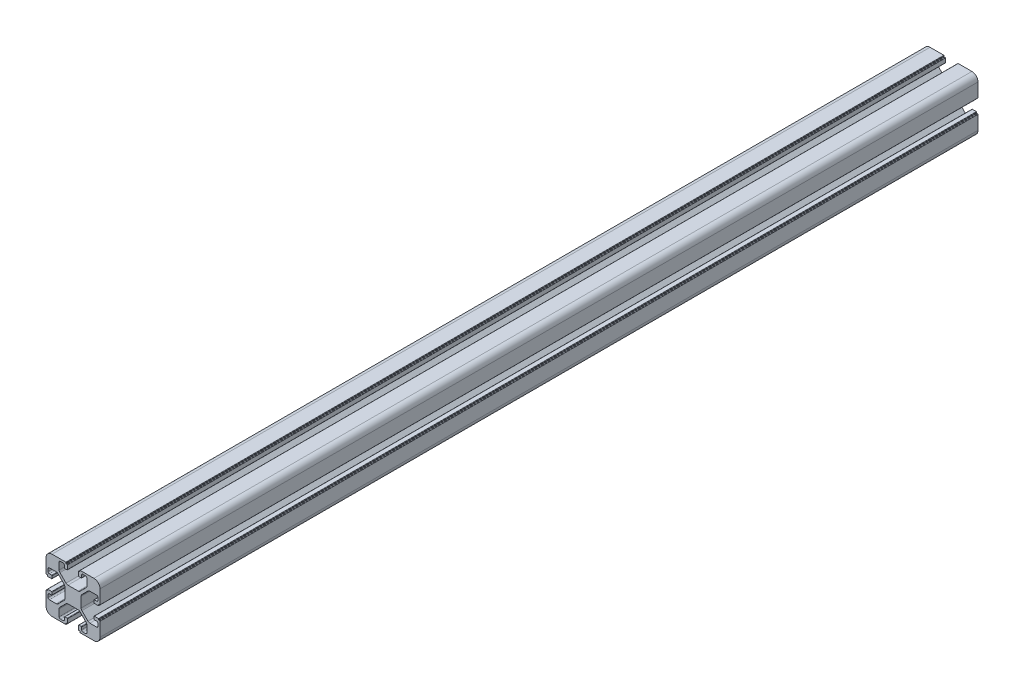
SolidWorks part; units mm, degrees
material "6063-T5"
ref_plane "Front Plane" through (0, 0, 0) normal (0, 0, 1) x (1, 0, 0)
ref_plane "Top Plane" through (0, 0, 0) normal (0, 1, 0) x (1, 0, 0)
ref_plane "Right Plane" through (0, 0, 0) normal (1, 0, 0) x (0, 0, -1)
sketch "Sketch2" plane through (0, 0, 0) normal (0, 0, 1) x (1, 0, 0)
  line L0 (4.5, 0) -> (14.7, 0)
  line L1 (40, 4.5) -> (40, 14.7)
  line L2 (35.5, 40) -> (25.3, 40)
  line L3 (0, 35.5) -> (0, 25.3)
  line L4 (15.9, 1.2) -> (15.9, 4.2)
  line L5 (24.1, 1.2) -> (24.1, 4.2)
  line L6 (38.8, 24.1) -> (35.8, 24.1)
  line L7 (35.5, 24.4) -> (35.5, 26.1)
  line L8 (14, 23.7574) -> (14, 16.2426)
  line L9 (16.2426, 14) -> (23.7574, 14)
  line L10 (26, 16.2426) -> (26, 23.7574)
  line L11 (13.4142, 14.8284) -> (8.9216, 10.3358)
  line L12 (23.7574, 26) -> (16.2426, 26)
  line L13 (4.5, 24.4) -> (4.5, 26.1)
  line L14 (1.2, 24.1) -> (4.2, 24.1)
  line L15 (15.9, 38.8) -> (15.9, 35.8)
  line L16 (14.8284, 26.5858) -> (10.3358, 31.0784)
  line L17 (13.4142, 25.1716) -> (8.9216, 29.6642)
  line L18 (14.8284, 13.4142) -> (10.3358, 8.9216)
  line L19 (25.1716, 13.4142) -> (29.6642, 8.9216)
  line L20 (26.5858, 14.8284) -> (31.0784, 10.3358)
  line L21 (26.5858, 25.1716) -> (31.0784, 29.6642)
  line L22 (25.1716, 26.5858) -> (29.6642, 31.0784)
  line L23 (24.1, 38.8) -> (24.1, 35.8)
  line L24 (14.7, 40) -> (4.5, 40)
  line L25 (25.3, 0) -> (35.5, 0)
  line L26 (38.8, 15.9) -> (35.8, 15.9)
  line L27 (40, 25.3) -> (40, 35.5)
  line L28 (1.2, 15.9) -> (4.2, 15.9)
  line L29 (0, 14.7) -> (0, 4.5)
  line L30 (4.5, 15.6) -> (4.5, 13.9)
  line L31 (35.5, 15.6) -> (35.5, 13.9)
  line L32 (15.6, 35.5) -> (13.9, 35.5)
  line L33 (24.4, 35.5) -> (26.1, 35.5)
  line L34 (15.6, 4.5) -> (13.9, 4.5)
  line L35 (24.4, 4.5) -> (26.1, 4.5)
  line L36 (12.6, 38.5) -> (10.75, 38.5)
  line L37 (1.5, 12.6) -> (1.5, 10.75)
  line L38 (27.4, 1.5) -> (29.25, 1.5)
  line L39 (38.5, 27.4) -> (38.5, 29.25)
  line L40 (38.5, 10.75) -> (38.5, 12.6)
  line L41 (29.25, 38.5) -> (27.4, 38.5)
  line L42 (1.5, 29.25) -> (1.5, 27.4)
  line L43 (10.75, 1.5) -> (12.6, 1.5)
  line L44 (35.8, 26.4) -> (37.5, 26.4)
  line L45 (35.8, 13.6) -> (37.5, 13.6)
  line L46 (4.2, 26.4) -> (2.5, 26.4)
  line L47 (13.6, 35.8) -> (13.6, 37.5)
  line L48 (26.4, 35.8) -> (26.4, 37.5)
  line L49 (4.2, 13.6) -> (2.5, 13.6)
  line L50 (13.6, 4.2) -> (13.6, 2.5)
  line L51 (26.4, 4.2) -> (26.4, 2.5)
  line L52 (9.75, 7.5074) -> (9.75, 2.5)
  line L53 (30.25, 7.5074) -> (30.25, 2.5)
  line L54 (9.75, 37.5) -> (9.75, 32.4926)
  line L55 (30.25, 37.5) -> (30.25, 32.4926)
  line L56 (32.4926, 30.25) -> (37.5, 30.25)
  line L57 (37.5, 9.75) -> (32.4926, 9.75)
  line L58 (2.5, 30.25) -> (7.5074, 30.25)
  line L59 (2.5, 9.75) -> (7.5074, 9.75)
  line L60 (31.55, 37.7) -> (31.55, 32.55)
  line L61 (32.55, 31.55) -> (37.7, 31.55)
  line L62 (1.3, 35.5) -> (1.3, 32.55)
  line L63 (4.5, 38.7) -> (7.45, 38.7)
  line L64 (32.55, 38.7) -> (35.5, 38.7)
  line L65 (38.7, 35.5) -> (38.7, 32.55)
  line L66 (8.45, 37.7) -> (8.45, 32.55)
  line L67 (2.3, 31.55) -> (7.45, 31.55)
  line L68 (1.3, 7.45) -> (1.3, 4.5)
  line L69 (2.3, 8.45) -> (7.45, 8.45)
  line L70 (8.45, 7.45) -> (8.45, 2.3)
  line L71 (4.5, 1.3) -> (7.45, 1.3)
  line L72 (31.55, 7.45) -> (31.55, 2.3)
  line L73 (32.55, 8.45) -> (37.7, 8.45)
  line L74 (38.7, 7.45) -> (38.7, 4.5)
  line L75 (32.55, 1.3) -> (35.5, 1.3)
  line L77 (14.9, 39.8) -> (14.9, 39.2)
  line L78 (15.1, 39) -> (15.7, 39)
  line L79 (25.1, 39.8) -> (25.1, 39.2)
  line L80 (24.9, 39) -> (24.3, 39)
  line L81 (25.1, 0.2) -> (25.1, 0.8)
  line L82 (24.9, 1) -> (24.3, 1)
  line L83 (14.9, 0.2) -> (14.9, 0.8)
  line L84 (15.1, 1) -> (15.7, 1)
  line L85 (0.2, 25.1) -> (0.8, 25.1)
  line L86 (1, 24.9) -> (1, 24.3)
  line L87 (0.2, 14.9) -> (0.8, 14.9)
  line L88 (1, 15.1) -> (1, 15.7)
  line L89 (39.8, 25.1) -> (39.2, 25.1)
  line L90 (39, 24.9) -> (39, 24.3)
  line L91 (39, 15.7) -> (39, 15.1)
  line L92 (39.2, 14.9) -> (39.8, 14.9)
  circle A0 centre (20, 20) radius 3.4
  arc A1 (1.3, 35.5) -> (4.5, 38.7) centre (4.5, 35.5) cw
  arc A2 (1.3, 4.5) -> (4.5, 1.3) centre (4.5, 4.5) ccw
  arc A3 (38.7, 4.5) -> (35.5, 1.3) centre (35.5, 4.5) cw
  arc A4 (35.5, 38.7) -> (38.7, 35.5) centre (35.5, 35.5) cw
  arc A5 (40, 35.5) -> (35.5, 40) centre (35.5, 35.5) ccw
  arc A6 (35.5, 0) -> (40, 4.5) centre (35.5, 4.5) ccw
  arc A7 (4.5, 0) -> (0, 4.5) centre (4.5, 4.5) cw
  arc A8 (4.5, 40) -> (0, 35.5) centre (4.5, 35.5) ccw
  arc A9 (13.4142, 14.8284) -> (14, 16.2426) centre (12, 16.2426) ccw
  arc A10 (7.5074, 9.75) -> (8.9216, 10.3358) centre (7.5074, 11.75) ccw
  arc A11 (9.75, 7.5074) -> (10.3358, 8.9216) centre (11.75, 7.5074) cw
  arc A12 (30.25, 7.5074) -> (29.6642, 8.9216) centre (28.25, 7.5074) ccw
  arc A13 (14.8284, 13.4142) -> (16.2426, 14) centre (16.2426, 12) cw
  arc A14 (25.1716, 13.4142) -> (23.7574, 14) centre (23.7574, 12) ccw
  arc A15 (32.4926, 9.75) -> (31.0784, 10.3358) centre (32.4926, 11.75) cw
  arc A16 (26.5858, 14.8284) -> (26, 16.2426) centre (28, 16.2426) cw
  arc A17 (32.4926, 30.25) -> (31.0784, 29.6642) centre (32.4926, 28.25) ccw
  arc A18 (26.5858, 25.1716) -> (26, 23.7574) centre (28, 23.7574) ccw
  arc A19 (13.4142, 25.1716) -> (14, 23.7574) centre (12, 23.7574) cw
  arc A20 (7.5074, 30.25) -> (8.9216, 29.6642) centre (7.5074, 28.25) cw
  arc A21 (9.75, 32.4926) -> (10.3358, 31.0784) centre (11.75, 32.4926) ccw
  arc A22 (30.25, 32.4926) -> (29.6642, 31.0784) centre (28.25, 32.4926) cw
  arc A23 (25.1716, 26.5858) -> (23.7574, 26) centre (23.7574, 28) cw
  arc A24 (14.8284, 26.5858) -> (16.2426, 26) centre (16.2426, 28) ccw
  arc A25 (37.7, 8.45) -> (38.7, 7.45) centre (37.7, 7.45) cw
  arc A26 (31.55, 2.3) -> (32.55, 1.3) centre (32.55, 2.3) ccw
  arc A27 (31.55, 7.45) -> (32.55, 8.45) centre (32.55, 7.45) cw
  arc A28 (8.45, 2.3) -> (7.45, 1.3) centre (7.45, 2.3) cw
  arc A29 (1.3, 7.45) -> (2.3, 8.45) centre (2.3, 7.45) cw
  arc A30 (7.45, 8.45) -> (8.45, 7.45) centre (7.45, 7.45) cw
  arc A31 (38.7, 32.55) -> (37.7, 31.55) centre (37.7, 32.55) cw
  arc A32 (31.55, 32.55) -> (32.55, 31.55) centre (32.55, 32.55) ccw
  arc A33 (31.55, 37.7) -> (32.55, 38.7) centre (32.55, 37.7) cw
  arc A34 (7.45, 38.7) -> (8.45, 37.7) centre (7.45, 37.7) cw
  arc A35 (8.45, 32.55) -> (7.45, 31.55) centre (7.45, 32.55) cw
  arc A36 (1.3, 32.55) -> (2.3, 31.55) centre (2.3, 32.55) ccw
  arc A37 (30.25, 2.5) -> (29.25, 1.5) centre (29.25, 2.5) cw
  arc A38 (26.4, 2.5) -> (27.4, 1.5) centre (27.4, 2.5) ccw
  arc A39 (13.6, 2.5) -> (12.6, 1.5) centre (12.6, 2.5) cw
  arc A40 (9.75, 2.5) -> (10.75, 1.5) centre (10.75, 2.5) ccw
  arc A41 (26.4, 37.5) -> (27.4, 38.5) centre (27.4, 37.5) cw
  arc A42 (30.25, 37.5) -> (29.25, 38.5) centre (29.25, 37.5) ccw
  arc A43 (37.5, 26.4) -> (38.5, 27.4) centre (37.5, 27.4) ccw
  arc A44 (37.5, 30.25) -> (38.5, 29.25) centre (37.5, 29.25) cw
  arc A45 (37.5, 13.6) -> (38.5, 12.6) centre (37.5, 12.6) cw
  arc A46 (37.5, 9.75) -> (38.5, 10.75) centre (37.5, 10.75) ccw
  arc A47 (2.5, 9.75) -> (1.5, 10.75) centre (2.5, 10.75) cw
  arc A48 (2.5, 13.6) -> (1.5, 12.6) centre (2.5, 12.6) ccw
  arc A49 (2.5, 26.4) -> (1.5, 27.4) centre (2.5, 27.4) cw
  arc A50 (2.5, 30.25) -> (1.5, 29.25) centre (2.5, 29.25) ccw
  arc A51 (9.75, 37.5) -> (10.75, 38.5) centre (10.75, 37.5) cw
  arc A52 (13.6, 37.5) -> (12.6, 38.5) centre (12.6, 37.5) ccw
  arc A53 (26.1, 35.5) -> (26.4, 35.8) centre (26.1, 35.8) ccw
  arc A54 (24.1, 35.8) -> (24.4, 35.5) centre (24.4, 35.8) ccw
  arc A55 (15.9, 35.8) -> (15.6, 35.5) centre (15.6, 35.8) cw
  arc A56 (13.9, 35.5) -> (13.6, 35.8) centre (13.9, 35.8) cw
  arc A57 (13.9, 4.5) -> (13.6, 4.2) centre (13.9, 4.2) ccw
  arc A58 (15.9, 4.2) -> (15.6, 4.5) centre (15.6, 4.2) ccw
  arc A59 (24.1, 4.2) -> (24.4, 4.5) centre (24.4, 4.2) cw
  arc A60 (26.1, 4.5) -> (26.4, 4.2) centre (26.1, 4.2) cw
  arc A61 (35.5, 13.9) -> (35.8, 13.6) centre (35.8, 13.9) ccw
  arc A62 (35.8, 15.9) -> (35.5, 15.6) centre (35.8, 15.6) ccw
  arc A63 (35.8, 24.1) -> (35.5, 24.4) centre (35.8, 24.4) cw
  arc A64 (35.5, 26.1) -> (35.8, 26.4) centre (35.8, 26.1) cw
  arc A65 (4.5, 13.9) -> (4.2, 13.6) centre (4.2, 13.9) cw
  arc A66 (4.2, 15.9) -> (4.5, 15.6) centre (4.2, 15.6) cw
  arc A67 (4.2, 24.1) -> (4.5, 24.4) centre (4.2, 24.4) ccw
  arc A68 (4.5, 26.1) -> (4.2, 26.4) centre (4.2, 26.1) ccw
  arc A69 (25.3, 0) -> (25.1, 0.2) centre (25.3, 0.2) cw
  arc A70 (25.1, 0.8) -> (24.9, 1) centre (24.9, 0.8) ccw
  arc A71 (24.3, 1) -> (24.1, 1.2) centre (24.3, 1.2) cw
  arc A72 (14.7, 0) -> (14.9, 0.2) centre (14.7, 0.2) ccw
  arc A73 (14.9, 0.8) -> (15.1, 1) centre (15.1, 0.8) cw
  arc A74 (15.7, 1) -> (15.9, 1.2) centre (15.7, 1.2) ccw
  arc A75 (39.8, 14.9) -> (40, 14.7) centre (39.8, 14.7) cw
  arc A76 (39, 15.1) -> (39.2, 14.9) centre (39.2, 15.1) ccw
  arc A77 (38.8, 15.9) -> (39, 15.7) centre (38.8, 15.7) cw
  arc A78 (0, 25.3) -> (0.2, 25.1) centre (0.2, 25.3) ccw
  arc A79 (0.8, 25.1) -> (1, 24.9) centre (0.8, 24.9) cw
  arc A80 (1, 24.3) -> (1.2, 24.1) centre (1.2, 24.3) ccw
  arc A81 (0, 14.7) -> (0.2, 14.9) centre (0.2, 14.7) cw
  arc A82 (0.8, 14.9) -> (1, 15.1) centre (0.8, 15.1) ccw
  arc A83 (1, 15.7) -> (1.2, 15.9) centre (1.2, 15.7) cw
  arc A84 (39, 24.3) -> (38.8, 24.1) centre (38.8, 24.3) cw
  arc A85 (39.2, 25.1) -> (39, 24.9) centre (39.2, 24.9) ccw
  arc A86 (40, 25.3) -> (39.8, 25.1) centre (39.8, 25.3) cw
  arc A87 (24.3, 39) -> (24.1, 38.8) centre (24.3, 38.8) ccw
  arc A88 (25.1, 39.2) -> (24.9, 39) centre (24.9, 39.2) cw
  arc A89 (25.3, 40) -> (25.1, 39.8) centre (25.3, 39.8) ccw
  arc A90 (14.9, 39.2) -> (15.1, 39) centre (15.1, 39.2) ccw
  arc A91 (15.7, 39) -> (15.9, 38.8) centre (15.7, 38.8) cw
  arc A92 (14.7, 40) -> (14.9, 39.8) centre (14.7, 39.8) cw
  point P93 (0, 0)
extrude "Boss-Extrude1" add sketch "Sketch2" along normal blind 50
sketch "Sketch3" plane through (0, 0, 50) normal (0, 0, 1) x (1, 0, 0)
  line L76 (25.3, 0) -> (35.5, 0)
  line L77 (40, 4.5) -> (40, 14.7)
  line L78 (39.8, 14.9) -> (39.2, 14.9)
  line L79 (39, 15.1) -> (39, 15.7)
  line L80 (38.8, 15.9) -> (35.8, 15.9)
  line L81 (35.5, 15.6) -> (35.5, 13.9)
  line L82 (35.8, 13.6) -> (37.5, 13.6)
  line L83 (38.5, 12.6) -> (38.5, 10.75)
  line L84 (37.5, 9.75) -> (32.4926, 9.75)
  line L85 (31.0784, 10.3358) -> (26.5858, 14.8284)
  line L86 (26, 16.2426) -> (26, 23.7574)
  line L87 (26.5858, 25.1716) -> (31.0784, 29.6642)
  line L88 (32.4926, 30.25) -> (37.5, 30.25)
  line L89 (38.5, 29.25) -> (38.5, 27.4)
  line L90 (37.5, 26.4) -> (35.8, 26.4)
  line L91 (35.5, 26.1) -> (35.5, 24.4)
  line L92 (35.8, 24.1) -> (38.8, 24.1)
  line L93 (39, 24.3) -> (39, 24.9)
  line L94 (39.2, 25.1) -> (39.8, 25.1)
  line L95 (40, 25.3) -> (40, 35.5)
  line L96 (35.5, 40) -> (25.3, 40)
  line L97 (25.1, 39.8) -> (25.1, 39.2)
  line L98 (24.9, 39) -> (24.3, 39)
  line L99 (24.1, 38.8) -> (24.1, 35.8)
  line L100 (24.4, 35.5) -> (26.1, 35.5)
  line L101 (26.4, 35.8) -> (26.4, 37.5)
  line L102 (27.4, 38.5) -> (29.25, 38.5)
  line L103 (30.25, 37.5) -> (30.25, 32.4926)
  line L104 (29.6642, 31.0784) -> (25.1716, 26.5858)
  line L105 (23.7574, 26) -> (16.2426, 26)
  line L106 (14.8284, 26.5858) -> (10.3358, 31.0784)
  line L107 (9.75, 32.4926) -> (9.75, 37.5)
  line L108 (10.75, 38.5) -> (12.6, 38.5)
  line L109 (13.6, 37.5) -> (13.6, 35.8)
  line L110 (13.9, 35.5) -> (15.6, 35.5)
  line L111 (15.9, 35.8) -> (15.9, 38.8)
  line L112 (15.7, 39) -> (15.1, 39)
  line L113 (14.9, 39.2) -> (14.9, 39.8)
  line L114 (14.7, 40) -> (4.5, 40)
  line L115 (0, 35.5) -> (0, 25.3)
  line L116 (0.2, 25.1) -> (0.8, 25.1)
  line L117 (1, 24.9) -> (1, 24.3)
  line L118 (1.2, 24.1) -> (4.2, 24.1)
  line L119 (4.5, 24.4) -> (4.5, 26.1)
  line L120 (4.2, 26.4) -> (2.5, 26.4)
  line L121 (1.5, 27.4) -> (1.5, 29.25)
  line L122 (2.5, 30.25) -> (7.5074, 30.25)
  line L123 (8.9216, 29.6642) -> (13.4142, 25.1716)
  line L124 (14, 23.7574) -> (14, 16.2426)
  line L125 (13.4142, 14.8284) -> (8.9216, 10.3358)
  line L126 (7.5074, 9.75) -> (2.5, 9.75)
  line L127 (1.5, 10.75) -> (1.5, 12.6)
  line L128 (2.5, 13.6) -> (4.2, 13.6)
  line L129 (4.5, 13.9) -> (4.5, 15.6)
  line L130 (4.2, 15.9) -> (1.2, 15.9)
  line L131 (1, 15.7) -> (1, 15.1)
  line L132 (0.8, 14.9) -> (0.2, 14.9)
  line L133 (0, 14.7) -> (0, 4.5)
  line L134 (4.5, 0) -> (14.7, 0)
  line L135 (14.9, 0.2) -> (14.9, 0.8)
  line L136 (15.1, 1) -> (15.7, 1)
  line L137 (15.9, 1.2) -> (15.9, 4.2)
  line L138 (15.6, 4.5) -> (13.9, 4.5)
  line L139 (13.6, 4.2) -> (13.6, 2.5)
  line L140 (12.6, 1.5) -> (10.75, 1.5)
  line L141 (9.75, 2.5) -> (9.75, 7.5074)
  line L142 (10.3358, 8.9216) -> (14.8284, 13.4142)
  line L143 (16.2426, 14) -> (23.7574, 14)
  line L144 (25.1716, 13.4142) -> (29.6642, 8.9216)
  line L145 (30.25, 7.5074) -> (30.25, 2.5)
  line L146 (29.25, 1.5) -> (27.4, 1.5)
  line L147 (26.4, 2.5) -> (26.4, 4.2)
  line L148 (26.1, 4.5) -> (24.4, 4.5)
  line L149 (24.1, 4.2) -> (24.1, 1.2)
  line L150 (24.3, 1) -> (24.9, 1)
  line L151 (25.1, 0.8) -> (25.1, 0.2)
  line L152 (25.3, 0) -> (35.5, 0)
  line L153 (40, 4.5) -> (40, 14.7)
  line L154 (39.8, 14.9) -> (39.2, 14.9)
  line L155 (39, 15.1) -> (39, 15.7)
  line L156 (38.8, 15.9) -> (35.8, 15.9)
  line L157 (35.5, 15.6) -> (35.5, 13.9)
  line L158 (35.8, 13.6) -> (37.5, 13.6)
  line L159 (38.5, 12.6) -> (38.5, 10.75)
  line L160 (37.5, 9.75) -> (32.4926, 9.75)
  line L161 (31.0784, 10.3358) -> (26.5858, 14.8284)
  line L162 (26, 16.2426) -> (26, 23.7574)
  line L163 (26.5858, 25.1716) -> (31.0784, 29.6642)
  line L164 (32.4926, 30.25) -> (37.5, 30.25)
  line L165 (38.5, 29.25) -> (38.5, 27.4)
  line L166 (37.5, 26.4) -> (35.8, 26.4)
  line L167 (35.5, 26.1) -> (35.5, 24.4)
  line L168 (35.8, 24.1) -> (38.8, 24.1)
  line L169 (39, 24.3) -> (39, 24.9)
  line L170 (39.2, 25.1) -> (39.8, 25.1)
  line L171 (40, 25.3) -> (40, 35.5)
  line L172 (35.5, 40) -> (25.3, 40)
  line L173 (25.1, 39.8) -> (25.1, 39.2)
  line L174 (24.9, 39) -> (24.3, 39)
  line L175 (24.1, 38.8) -> (24.1, 35.8)
  line L176 (24.4, 35.5) -> (26.1, 35.5)
  line L177 (26.4, 35.8) -> (26.4, 37.5)
  line L178 (27.4, 38.5) -> (29.25, 38.5)
  line L179 (30.25, 37.5) -> (30.25, 32.4926)
  line L180 (29.6642, 31.0784) -> (25.1716, 26.5858)
  line L181 (23.7574, 26) -> (16.2426, 26)
  line L182 (14.8284, 26.5858) -> (10.3358, 31.0784)
  line L183 (9.75, 32.4926) -> (9.75, 37.5)
  line L184 (10.75, 38.5) -> (12.6, 38.5)
  line L185 (13.6, 37.5) -> (13.6, 35.8)
  line L186 (13.9, 35.5) -> (15.6, 35.5)
  line L187 (15.9, 35.8) -> (15.9, 38.8)
  line L188 (15.7, 39) -> (15.1, 39)
  line L189 (14.9, 39.2) -> (14.9, 39.8)
  line L190 (14.7, 40) -> (4.5, 40)
  line L191 (0, 35.5) -> (0, 25.3)
  line L192 (0.2, 25.1) -> (0.8, 25.1)
  line L193 (1, 24.9) -> (1, 24.3)
  line L194 (1.2, 24.1) -> (4.2, 24.1)
  line L195 (4.5, 24.4) -> (4.5, 26.1)
  line L196 (4.2, 26.4) -> (2.5, 26.4)
  line L197 (1.5, 27.4) -> (1.5, 29.25)
  line L198 (2.5, 30.25) -> (7.5074, 30.25)
  line L199 (8.9216, 29.6642) -> (13.4142, 25.1716)
  line L200 (14, 23.7574) -> (14, 16.2426)
  line L201 (13.4142, 14.8284) -> (8.9216, 10.3358)
  line L202 (7.5074, 9.75) -> (2.5, 9.75)
  line L203 (1.5, 10.75) -> (1.5, 12.6)
  line L204 (2.5, 13.6) -> (4.2, 13.6)
  line L205 (4.5, 13.9) -> (4.5, 15.6)
  line L206 (4.2, 15.9) -> (1.2, 15.9)
  line L207 (1, 15.7) -> (1, 15.1)
  line L208 (0.8, 14.9) -> (0.2, 14.9)
  line L209 (0, 14.7) -> (0, 4.5)
  line L210 (4.5, 0) -> (14.7, 0)
  line L211 (14.9, 0.2) -> (14.9, 0.8)
  line L212 (15.1, 1) -> (15.7, 1)
  line L213 (15.9, 1.2) -> (15.9, 4.2)
  line L214 (15.6, 4.5) -> (13.9, 4.5)
  line L215 (13.6, 4.2) -> (13.6, 2.5)
  line L216 (12.6, 1.5) -> (10.75, 1.5)
  line L217 (9.75, 2.5) -> (9.75, 7.5074)
  line L218 (10.3358, 8.9216) -> (14.8284, 13.4142)
  line L219 (16.2426, 14) -> (23.7574, 14)
  line L220 (25.1716, 13.4142) -> (29.6642, 8.9216)
  line L221 (30.25, 7.5074) -> (30.25, 2.5)
  line L222 (29.25, 1.5) -> (27.4, 1.5)
  line L223 (26.4, 2.5) -> (26.4, 4.2)
  line L224 (26.1, 4.5) -> (24.4, 4.5)
  line L225 (24.1, 4.2) -> (24.1, 1.2)
  line L226 (24.3, 1) -> (24.9, 1)
  line L227 (25.1, 0.8) -> (25.1, 0.2)
  arc A76 (25.1, 0.2) -> (25.3, 0) centre (25.3, 0.2) ccw
  arc A77 (35.5, 0) -> (40, 4.5) centre (35.5, 4.5) ccw
  arc A78 (40, 14.7) -> (39.8, 14.9) centre (39.8, 14.7) ccw
  arc A79 (39, 15.1) -> (39.2, 14.9) centre (39.2, 15.1) ccw
  arc A80 (39, 15.7) -> (38.8, 15.9) centre (38.8, 15.7) ccw
  arc A81 (35.8, 15.9) -> (35.5, 15.6) centre (35.8, 15.6) ccw
  arc A82 (35.5, 13.9) -> (35.8, 13.6) centre (35.8, 13.9) ccw
  arc A83 (38.5, 12.6) -> (37.5, 13.6) centre (37.5, 12.6) ccw
  arc A84 (37.5, 9.75) -> (38.5, 10.75) centre (37.5, 10.75) ccw
  arc A85 (31.0784, 10.3358) -> (32.4926, 9.75) centre (32.4926, 11.75) ccw
  arc A86 (26, 16.2426) -> (26.5858, 14.8284) centre (28, 16.2426) ccw
  arc A87 (26.5858, 25.1716) -> (26, 23.7574) centre (28, 23.7574) ccw
  arc A88 (32.4926, 30.25) -> (31.0784, 29.6642) centre (32.4926, 28.25) ccw
  arc A89 (38.5, 29.25) -> (37.5, 30.25) centre (37.5, 29.25) ccw
  arc A90 (37.5, 26.4) -> (38.5, 27.4) centre (37.5, 27.4) ccw
  arc A91 (35.8, 26.4) -> (35.5, 26.1) centre (35.8, 26.1) ccw
  arc A92 (35.5, 24.4) -> (35.8, 24.1) centre (35.8, 24.4) ccw
  arc A93 (38.8, 24.1) -> (39, 24.3) centre (38.8, 24.3) ccw
  arc A94 (39.2, 25.1) -> (39, 24.9) centre (39.2, 24.9) ccw
  arc A95 (39.8, 25.1) -> (40, 25.3) centre (39.8, 25.3) ccw
  arc A96 (40, 35.5) -> (35.5, 40) centre (35.5, 35.5) ccw
  arc A97 (25.3, 40) -> (25.1, 39.8) centre (25.3, 39.8) ccw
  arc A98 (24.9, 39) -> (25.1, 39.2) centre (24.9, 39.2) ccw
  arc A99 (24.3, 39) -> (24.1, 38.8) centre (24.3, 38.8) ccw
  arc A100 (24.1, 35.8) -> (24.4, 35.5) centre (24.4, 35.8) ccw
  arc A101 (26.1, 35.5) -> (26.4, 35.8) centre (26.1, 35.8) ccw
  arc A102 (27.4, 38.5) -> (26.4, 37.5) centre (27.4, 37.5) ccw
  arc A103 (30.25, 37.5) -> (29.25, 38.5) centre (29.25, 37.5) ccw
  arc A104 (29.6642, 31.0784) -> (30.25, 32.4926) centre (28.25, 32.4926) ccw
  arc A105 (23.7574, 26) -> (25.1716, 26.5858) centre (23.7574, 28) ccw
  arc A106 (14.8284, 26.5858) -> (16.2426, 26) centre (16.2426, 28) ccw
  arc A107 (9.75, 32.4926) -> (10.3358, 31.0784) centre (11.75, 32.4926) ccw
  arc A108 (10.75, 38.5) -> (9.75, 37.5) centre (10.75, 37.5) ccw
  arc A109 (13.6, 37.5) -> (12.6, 38.5) centre (12.6, 37.5) ccw
  arc A110 (13.6, 35.8) -> (13.9, 35.5) centre (13.9, 35.8) ccw
  arc A111 (15.6, 35.5) -> (15.9, 35.8) centre (15.6, 35.8) ccw
  arc A112 (15.9, 38.8) -> (15.7, 39) centre (15.7, 38.8) ccw
  arc A113 (14.9, 39.2) -> (15.1, 39) centre (15.1, 39.2) ccw
  arc A114 (14.9, 39.8) -> (14.7, 40) centre (14.7, 39.8) ccw
  arc A115 (4.5, 40) -> (0, 35.5) centre (4.5, 35.5) ccw
  arc A116 (0, 25.3) -> (0.2, 25.1) centre (0.2, 25.3) ccw
  arc A117 (1, 24.9) -> (0.8, 25.1) centre (0.8, 24.9) ccw
  arc A118 (1, 24.3) -> (1.2, 24.1) centre (1.2, 24.3) ccw
  arc A119 (4.2, 24.1) -> (4.5, 24.4) centre (4.2, 24.4) ccw
  arc A120 (4.5, 26.1) -> (4.2, 26.4) centre (4.2, 26.1) ccw
  arc A121 (1.5, 27.4) -> (2.5, 26.4) centre (2.5, 27.4) ccw
  arc A122 (2.5, 30.25) -> (1.5, 29.25) centre (2.5, 29.25) ccw
  arc A123 (8.9216, 29.6642) -> (7.5074, 30.25) centre (7.5074, 28.25) ccw
  arc A124 (14, 23.7574) -> (13.4142, 25.1716) centre (12, 23.7574) ccw
  arc A125 (13.4142, 14.8284) -> (14, 16.2426) centre (12, 16.2426) ccw
  arc A126 (7.5074, 9.75) -> (8.9216, 10.3358) centre (7.5074, 11.75) ccw
  arc A127 (1.5, 10.75) -> (2.5, 9.75) centre (2.5, 10.75) ccw
  arc A128 (2.5, 13.6) -> (1.5, 12.6) centre (2.5, 12.6) ccw
  arc A129 (4.2, 13.6) -> (4.5, 13.9) centre (4.2, 13.9) ccw
  arc A130 (4.5, 15.6) -> (4.2, 15.9) centre (4.2, 15.6) ccw
  arc A131 (1.2, 15.9) -> (1, 15.7) centre (1.2, 15.7) ccw
  arc A132 (0.8, 14.9) -> (1, 15.1) centre (0.8, 15.1) ccw
  arc A133 (0.2, 14.9) -> (0, 14.7) centre (0.2, 14.7) ccw
  arc A134 (0, 4.5) -> (4.5, 0) centre (4.5, 4.5) ccw
  arc A135 (14.7, 0) -> (14.9, 0.2) centre (14.7, 0.2) ccw
  arc A136 (15.1, 1) -> (14.9, 0.8) centre (15.1, 0.8) ccw
  arc A137 (15.7, 1) -> (15.9, 1.2) centre (15.7, 1.2) ccw
  arc A138 (15.9, 4.2) -> (15.6, 4.5) centre (15.6, 4.2) ccw
  arc A139 (13.9, 4.5) -> (13.6, 4.2) centre (13.9, 4.2) ccw
  arc A140 (12.6, 1.5) -> (13.6, 2.5) centre (12.6, 2.5) ccw
  arc A141 (9.75, 2.5) -> (10.75, 1.5) centre (10.75, 2.5) ccw
  arc A142 (10.3358, 8.9216) -> (9.75, 7.5074) centre (11.75, 7.5074) ccw
  arc A143 (16.2426, 14) -> (14.8284, 13.4142) centre (16.2426, 12) ccw
  arc A144 (25.1716, 13.4142) -> (23.7574, 14) centre (23.7574, 12) ccw
  arc A145 (30.25, 7.5074) -> (29.6642, 8.9216) centre (28.25, 7.5074) ccw
  arc A146 (29.25, 1.5) -> (30.25, 2.5) centre (29.25, 2.5) ccw
  arc A147 (26.4, 2.5) -> (27.4, 1.5) centre (27.4, 2.5) ccw
  arc A148 (26.4, 4.2) -> (26.1, 4.5) centre (26.1, 4.2) ccw
  arc A149 (24.4, 4.5) -> (24.1, 4.2) centre (24.4, 4.2) ccw
  arc A150 (24.1, 1.2) -> (24.3, 1) centre (24.3, 1.2) ccw
  arc A151 (25.1, 0.8) -> (24.9, 1) centre (24.9, 0.8) ccw
  arc A152 (25.1, 0.2) -> (25.3, 0) centre (25.3, 0.2) ccw
  arc A153 (35.5, 0) -> (40, 4.5) centre (35.5, 4.5) ccw
  arc A154 (40, 14.7) -> (39.8, 14.9) centre (39.8, 14.7) ccw
  arc A155 (39, 15.1) -> (39.2, 14.9) centre (39.2, 15.1) ccw
  arc A156 (39, 15.7) -> (38.8, 15.9) centre (38.8, 15.7) ccw
  arc A157 (35.8, 15.9) -> (35.5, 15.6) centre (35.8, 15.6) ccw
  arc A158 (35.5, 13.9) -> (35.8, 13.6) centre (35.8, 13.9) ccw
  arc A159 (38.5, 12.6) -> (37.5, 13.6) centre (37.5, 12.6) ccw
  arc A160 (37.5, 9.75) -> (38.5, 10.75) centre (37.5, 10.75) ccw
  arc A161 (31.0784, 10.3358) -> (32.4926, 9.75) centre (32.4926, 11.75) ccw
  arc A162 (26, 16.2426) -> (26.5858, 14.8284) centre (28, 16.2426) ccw
  arc A163 (26.5858, 25.1716) -> (26, 23.7574) centre (28, 23.7574) ccw
  arc A164 (32.4926, 30.25) -> (31.0784, 29.6642) centre (32.4926, 28.25) ccw
  arc A165 (38.5, 29.25) -> (37.5, 30.25) centre (37.5, 29.25) ccw
  arc A166 (37.5, 26.4) -> (38.5, 27.4) centre (37.5, 27.4) ccw
  arc A167 (35.8, 26.4) -> (35.5, 26.1) centre (35.8, 26.1) ccw
  arc A168 (35.5, 24.4) -> (35.8, 24.1) centre (35.8, 24.4) ccw
  arc A169 (38.8, 24.1) -> (39, 24.3) centre (38.8, 24.3) ccw
  arc A170 (39.2, 25.1) -> (39, 24.9) centre (39.2, 24.9) ccw
  arc A171 (39.8, 25.1) -> (40, 25.3) centre (39.8, 25.3) ccw
  arc A172 (40, 35.5) -> (35.5, 40) centre (35.5, 35.5) ccw
  arc A173 (25.3, 40) -> (25.1, 39.8) centre (25.3, 39.8) ccw
  arc A174 (24.9, 39) -> (25.1, 39.2) centre (24.9, 39.2) ccw
  arc A175 (24.3, 39) -> (24.1, 38.8) centre (24.3, 38.8) ccw
  arc A176 (24.1, 35.8) -> (24.4, 35.5) centre (24.4, 35.8) ccw
  arc A177 (26.1, 35.5) -> (26.4, 35.8) centre (26.1, 35.8) ccw
  arc A178 (27.4, 38.5) -> (26.4, 37.5) centre (27.4, 37.5) ccw
  arc A179 (30.25, 37.5) -> (29.25, 38.5) centre (29.25, 37.5) ccw
  arc A180 (29.6642, 31.0784) -> (30.25, 32.4926) centre (28.25, 32.4926) ccw
  arc A181 (23.7574, 26) -> (25.1716, 26.5858) centre (23.7574, 28) ccw
  arc A182 (14.8284, 26.5858) -> (16.2426, 26) centre (16.2426, 28) ccw
  arc A183 (9.75, 32.4926) -> (10.3358, 31.0784) centre (11.75, 32.4926) ccw
  arc A184 (10.75, 38.5) -> (9.75, 37.5) centre (10.75, 37.5) ccw
  arc A185 (13.6, 37.5) -> (12.6, 38.5) centre (12.6, 37.5) ccw
  arc A186 (13.6, 35.8) -> (13.9, 35.5) centre (13.9, 35.8) ccw
  arc A187 (15.6, 35.5) -> (15.9, 35.8) centre (15.6, 35.8) ccw
  arc A188 (15.9, 38.8) -> (15.7, 39) centre (15.7, 38.8) ccw
  arc A189 (14.9, 39.2) -> (15.1, 39) centre (15.1, 39.2) ccw
  arc A190 (14.9, 39.8) -> (14.7, 40) centre (14.7, 39.8) ccw
  arc A191 (4.5, 40) -> (0, 35.5) centre (4.5, 35.5) ccw
  arc A192 (0, 25.3) -> (0.2, 25.1) centre (0.2, 25.3) ccw
  arc A193 (1, 24.9) -> (0.8, 25.1) centre (0.8, 24.9) ccw
  arc A194 (1, 24.3) -> (1.2, 24.1) centre (1.2, 24.3) ccw
  arc A195 (4.2, 24.1) -> (4.5, 24.4) centre (4.2, 24.4) ccw
  arc A196 (4.5, 26.1) -> (4.2, 26.4) centre (4.2, 26.1) ccw
  arc A197 (1.5, 27.4) -> (2.5, 26.4) centre (2.5, 27.4) ccw
  arc A198 (2.5, 30.25) -> (1.5, 29.25) centre (2.5, 29.25) ccw
  arc A199 (8.9216, 29.6642) -> (7.5074, 30.25) centre (7.5074, 28.25) ccw
  arc A200 (14, 23.7574) -> (13.4142, 25.1716) centre (12, 23.7574) ccw
  arc A201 (13.4142, 14.8284) -> (14, 16.2426) centre (12, 16.2426) ccw
  arc A202 (7.5074, 9.75) -> (8.9216, 10.3358) centre (7.5074, 11.75) ccw
  arc A203 (1.5, 10.75) -> (2.5, 9.75) centre (2.5, 10.75) ccw
  arc A204 (2.5, 13.6) -> (1.5, 12.6) centre (2.5, 12.6) ccw
  arc A205 (4.2, 13.6) -> (4.5, 13.9) centre (4.2, 13.9) ccw
  arc A206 (4.5, 15.6) -> (4.2, 15.9) centre (4.2, 15.6) ccw
  arc A207 (1.2, 15.9) -> (1, 15.7) centre (1.2, 15.7) ccw
  arc A208 (0.8, 14.9) -> (1, 15.1) centre (0.8, 15.1) ccw
  arc A209 (0.2, 14.9) -> (0, 14.7) centre (0.2, 14.7) ccw
  arc A210 (0, 4.5) -> (4.5, 0) centre (4.5, 4.5) ccw
  arc A211 (14.7, 0) -> (14.9, 0.2) centre (14.7, 0.2) ccw
  arc A212 (15.1, 1) -> (14.9, 0.8) centre (15.1, 0.8) ccw
  arc A213 (15.7, 1) -> (15.9, 1.2) centre (15.7, 1.2) ccw
  arc A214 (15.9, 4.2) -> (15.6, 4.5) centre (15.6, 4.2) ccw
  arc A215 (13.9, 4.5) -> (13.6, 4.2) centre (13.9, 4.2) ccw
  arc A216 (12.6, 1.5) -> (13.6, 2.5) centre (12.6, 2.5) ccw
  arc A217 (9.75, 2.5) -> (10.75, 1.5) centre (10.75, 2.5) ccw
  arc A218 (10.3358, 8.9216) -> (9.75, 7.5074) centre (11.75, 7.5074) ccw
  arc A219 (16.2426, 14) -> (14.8284, 13.4142) centre (16.2426, 12) ccw
  arc A220 (25.1716, 13.4142) -> (23.7574, 14) centre (23.7574, 12) ccw
  arc A221 (30.25, 7.5074) -> (29.6642, 8.9216) centre (28.25, 7.5074) ccw
  arc A222 (29.25, 1.5) -> (30.25, 2.5) centre (29.25, 2.5) ccw
  arc A223 (26.4, 2.5) -> (27.4, 1.5) centre (27.4, 2.5) ccw
  arc A224 (26.4, 4.2) -> (26.1, 4.5) centre (26.1, 4.2) ccw
  arc A225 (24.4, 4.5) -> (24.1, 4.2) centre (24.4, 4.2) ccw
  arc A226 (24.1, 1.2) -> (24.3, 1) centre (24.3, 1.2) ccw
  arc A227 (25.1, 0.8) -> (24.9, 1) centre (24.9, 0.8) ccw
  dimension "D1" = 0
extrude "Boss-Extrude2" add sketch "Sketch3" along normal blind 600
